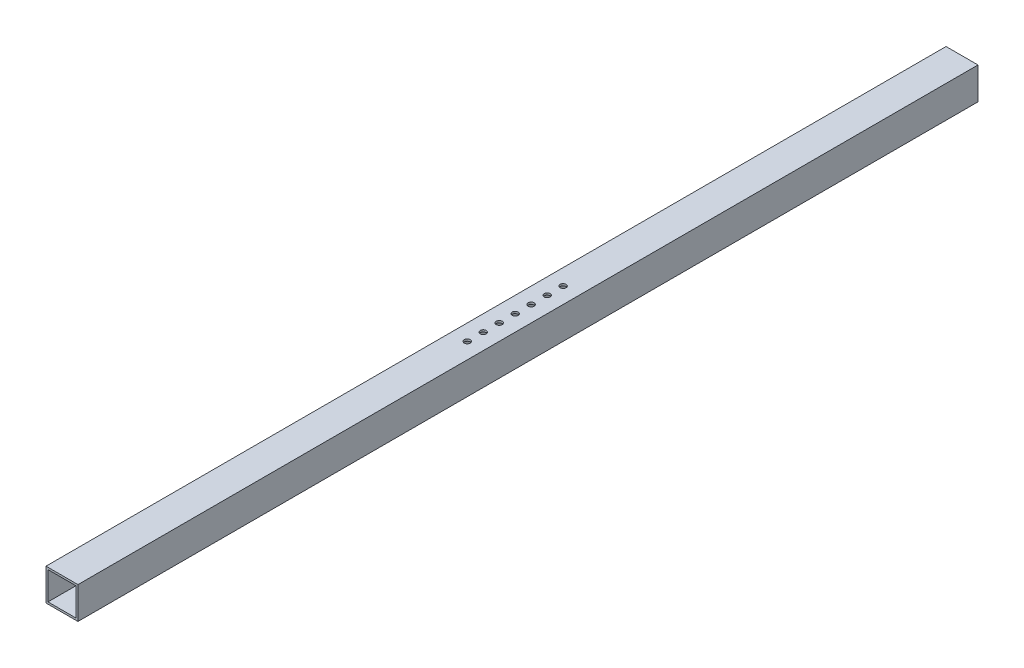
SolidWorks part; units mm, degrees
material "ALUMINUM 6061-T6"
ref_plane "Front Plane" through (0, 0, 0) normal (0, 0, 1) x (1, 0, 0)
ref_plane "Top Plane" through (0, 0, 0) normal (0, 1, 0) x (1, 0, 0)
ref_plane "Right Plane" through (0, 0, 0) normal (1, 0, 0) x (0, 0, -1)
sketch "Sketch1" plane through (0, 0, 0) normal (0, 0, 1) x (1, 0, 0)
  line L0 (11.1125, -11.1125) -> (11.1125, 11.1125)
  line L1 (-12.7, -12.7) -> (12.7, -12.7)
  line L2 (-12.7, -12.7) -> (-12.7, 12.7)
  line L3 (-12.7, 12.7) -> (12.7, 12.7)
  line L4 (12.7, -12.7) -> (12.7, 12.7)
  line L5 (-12.7, -12.7) -> (12.7, 12.7) construction
  line L6 (-12.7, 12.7) -> (12.7, -12.7) construction
  line L7 (-11.1125, 11.1125) -> (11.1125, 11.1125)
  line L8 (-11.1125, -11.1125) -> (-11.1125, 11.1125)
  line L9 (-11.1125, -11.1125) -> (11.1125, -11.1125)
  point P0 (0, 0)
  dimension "D1" = 25.4
  dimension "D2" = 25.4
  dimension "D3" = 1.5875
extrude "Boss-Extrude1" add sketch "Sketch1" along normal mid plane 715.518
sketch "Sketch2" plane through (0, -12.7, 0) normal (0, -1, 0) x (1, 0, 0)
  line L0 (-12.7, 357.759) -> (12.7, 357.759) construction
  circle A0 centre (0, -40.6332) radius 2.3812
  circle A1 centre (0, -27.9332) radius 2.3812
  circle A2 centre (0, -15.2332) radius 2.3812
  circle A3 centre (0, -2.5332) radius 2.3812
  circle A4 centre (0, 10.1668) radius 2.3812
  circle A5 centre (0, 22.8668) radius 2.3812
  circle A6 centre (0, 35.5668) radius 2.3812
  dimension "D1" = 4.7625
  dimension "D2" = 12.7
  dimension "D3" = 12.7
  dimension "D4" = 12.7
  dimension "D5" = 12.7
  dimension "D6" = 12.7
  dimension "D7" = 12.7
  dimension "D8" = 360.2922
extrude "Cut-Extrude1" cut sketch "Sketch2" against normal through all
